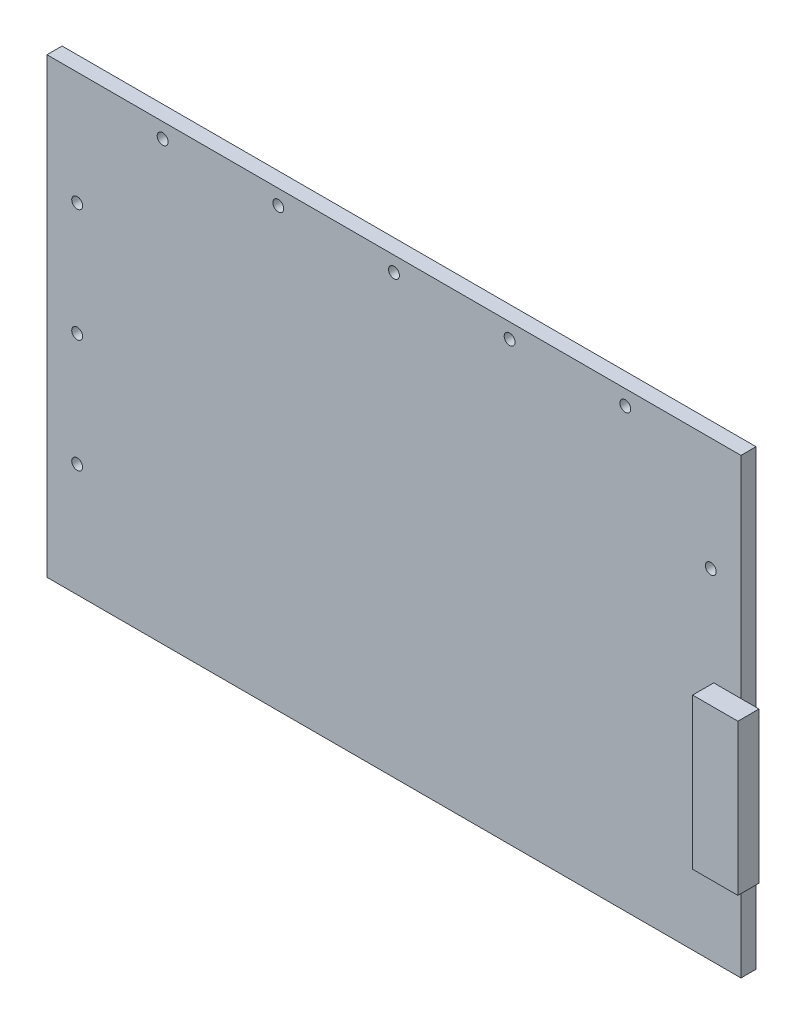
SolidWorks part; units mm, degrees
ref_plane "Płaszczyzna przednia" through (0, 0, 0) normal (0, 0, 1) x (1, 0, 0)
ref_plane "Płaszczyzna górna" through (0, 0, 0) normal (0, 1, 0) x (1, 0, 0)
ref_plane "Płaszczyzna prawa" through (0, 0, 0) normal (1, 0, 0) x (0, 0, -1)
sketch "Szkic1" plane through (0, 0, 0) normal (0, 0, 1) x (1, 0, 0)
  line L1 (-115, -75) -> (115, -75)
  line L2 (-115, -75) -> (-115, 75)
  line L3 (-115, 75) -> (115, 75)
  line L4 (115, -75) -> (115, 75)
  line L5 (0, 75) -> (0, -75) construction
  line L6 (-115, 0) -> (115, 0) construction
  point P0 (0, 0)
  dimension "D1" = 230
  dimension "D2" = 150
extrude "Dodanie-wyciągnięcie1" add sketch "Szkic1" along normal blind 5
sketch "Szkic3" plane through (0, 0, 0) normal (0, 0, -1) x (-1, 0, 0)
  line L0 (0, 75) -> (0, -75) construction
  line L1 (-115, 75) -> (115, 75) construction
  line L2 (115, -75) -> (-115, -75) construction
  point P0 (105, 37.5)
  point P1 (105, 0)
  point P3 (105, -37.5)
  point P16 (-105, 0)
  point P17 (-105, 37.5)
hole_wizard "Pogłębienie walcowe pod M3 Śrubę z łbem stożkowym ściętym1" positions "Szkic3" profile "Szkic4" counterbore size "M3" standard "DIN"
sketch "Szkic4" plane through (-105, 37.5, 0) normal (1, 0, 0) x (0, 1, 0)
  line L0 (0, 0) -> (0, 7.7815)
  line L1 (0, 7.7815) -> (1.8, 6.7)
  line L2 (1.8, 6.7) -> (1.8, 2.4)
  line L3 (1.8, 2.4) -> (3.5, 2.4)
  line L4 (3.5, 2.4) -> (3.5, 0)
  line L5 (3.5, 0) -> (0, 0)
  line L10 (0, 7.7815) -> (-1.8, 6.7) construction
  line L11 (0, -6.35) -> (0, 107.95) construction
  dimension "Średnica otworu" = 3.6
  dimension "Głębokość otworu" = 6.7
  dimension "Średnica pogłębienia walcowego" = 7
  dimension "Głębokość pogłębienia walcowego" = 2.4
  dimension "Kąt wiertła" = 118
sketch "Szkic5" plane through (0, 0, 0) normal (0, 0, -1) x (-1, 0, 0)
  line L0 (-115, 75) -> (115, 75) construction
  line L1 (-115, -75) -> (-115, 75) construction
  point P0 (-76.6667, 70)
  point P5 (-38.3333, 70)
  point P7 (0, 70)
  point P8 (38.3333, 70)
  point P9 (76.6667, 70)
  dimension "D1" = 5
  dimension "D2" = 38.3333
  dimension "D3" = 5
hole_wizard "Pogłębienie walcowe pod M3 Śrubę z łbem stożkowym ściętym2" positions "Szkic5" profile "Szkic6" counterbore size "M3" standard "DIN"
sketch "Szkic6" plane through (76.6667, 70, 0) normal (1, 0, 0) x (0, 1, 0)
  line L0 (0, 0) -> (0, 7.7815)
  line L1 (0, 7.7815) -> (1.8, 6.7)
  line L2 (1.8, 6.7) -> (1.8, 2.4)
  line L3 (1.8, 2.4) -> (3.5, 2.4)
  line L4 (3.5, 2.4) -> (3.5, 0)
  line L5 (3.5, 0) -> (0, 0)
  line L10 (0, 7.7815) -> (-1.8, 6.7) construction
  line L11 (0, -6.35) -> (0, 107.95) construction
  dimension "Średnica otworu" = 3.6
  dimension "Głębokość otworu" = 6.7
  dimension "Średnica pogłębienia walcowego" = 7
  dimension "Głębokość pogłębienia walcowego" = 2.4
  dimension "Kąt wiertła" = 118
sketch "Szkic7" plane through (0, 0, 5) normal (0, 0, 1) x (1, 0, 0)
  line L0 (120.9805, -44.8014) -> (120.9805, 5.1986)
  line L14 (120.9805, -44.8014) -> (120.9805, 5.1986)
  line L15 (120.9805, 5.1986) -> (105.9805, 5.1986)
  line L16 (105.9805, 5.1986) -> (105.9805, -44.8014)
  line L17 (105.9805, -44.8014) -> (120.9805, -44.8014)
  line L21 (120.9805, 5.1986) -> (105.9805, 5.1986)
  line L22 (105.9805, 5.1986) -> (105.9805, -44.8014)
  line L23 (105.9805, -44.8014) -> (120.9805, -44.8014)
  dimension "D2" = 0
extrude "Dodanie-wyciągnięcie3" add sketch "Szkic7" along normal blind 7
sketch "Szkic8" plane through (0, -44.8014, 0) normal (0, -1, 0) x (1, 0, 0)
  line L0 (105.9805, 12) -> (110, 5) construction
  point P4 (107.9902, 8.5)
hole_wizard "Otwory ustalające Ø4.0mm1" positions "Szkic8" profile "Szkic9" hole size "Ø4.0" standard "DIN"
sketch "Szkic9" plane through (107.9902, -44.8014, 8.5) normal (1, 0, 0) x (0, 0, -1)
  line L0 (0, 0) -> (0, 6.7)
  line L1 (0, 6.7) -> (2, 6.7)
  line L2 (2, 6.7) -> (2, 0)
  line L5 (2, 0) -> (0, 0)
  line L10 (0, 6.7) -> (-2, 6.7) construction
  line L11 (0, -6.35) -> (0, 107.95) construction
  dimension "Średnica otworu" = 4
  dimension "Głębokość otworu" = 6.7
  dimension "Kąt wiertła" = 180
